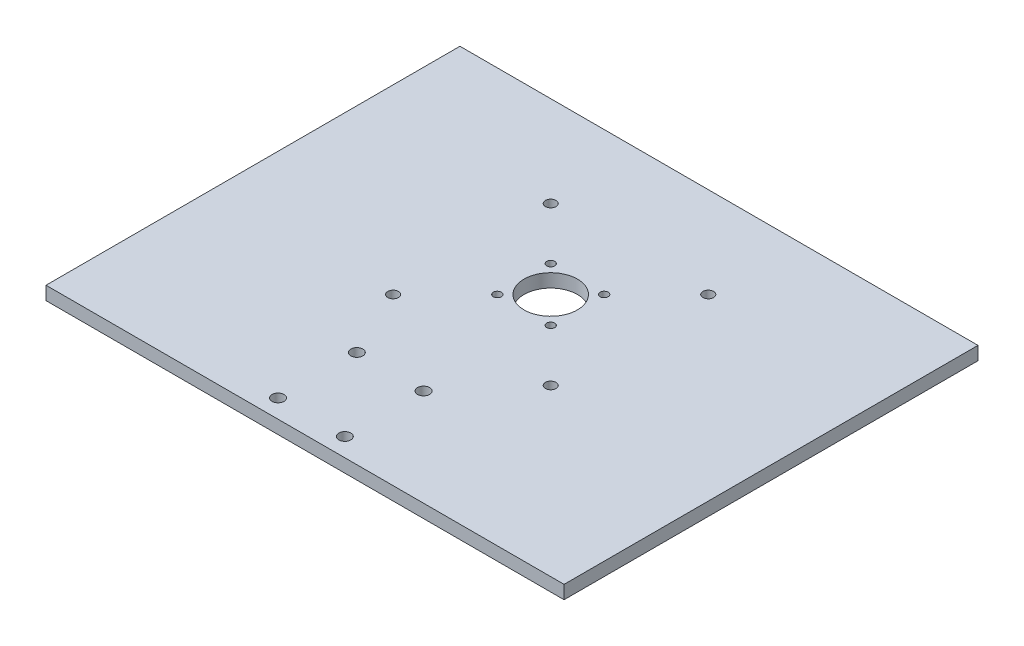
SolidWorks part; units mm, degrees
ref_plane "Front Plane" through (0, 0, 0) normal (0, 0, 1) x (1, 0, 0)
ref_plane "Top Plane" through (0, 0, 0) normal (0, 1, 0) x (1, 0, 0)
ref_plane "Right Plane" through (0, 0, 0) normal (1, 0, 0) x (0, 0, -1)
sketch "Sketch1" plane through (0, 0, 0) normal (0, 1, 0) x (1, 0, 0)
  line L1 (0, 0) -> (194, 0)
  line L2 (0, 0) -> (0, 155)
  line L3 (0, 155) -> (194, 155)
  line L4 (194, 0) -> (194, 155)
  dimension "D1" = 155
  dimension "D2" = 194
extrude "Boss-Extrude1" add sketch "Sketch1" along normal blind 5
sketch "Sketch2" plane through (0, 5, 0) normal (0, 1, 0) x (1, 0, 0)
  line L0 (194, 155) -> (0, 155) construction
  line L1 (0, 0) -> (194, 0) construction
  line L2 (68, 60) -> (68, 64) construction
  line L3 (127, 123) -> (127, 119) construction
  line L4 (70, 62) -> (66, 62) construction
  line L5 (125, 121) -> (129, 121) construction
  line L6 (68, 60) -> (68, 170.8676) construction
  circle A0 centre (68, 121) radius 2
  circle A1 centre (127, 121) radius 2
  circle A2 centre (68, 62) radius 2
  circle A3 centre (127, 62) radius 2
  point P4 (97, 155)
  dimension "D4" = 4
  dimension "D1" = 59
  dimension "D2" = 29
  dimension "D6" = 62
  dimension "D7" = 59
  dimension "D3" = 2
extrude "Cut-Extrude1" cut sketch "Sketch2" against normal through all
sketch "Sketch3" plane through (0, 5, 0) normal (0, 1, 0) x (1, 0, 0)
  circle A0 centre (97.5, 91.5) radius 10
  circle A1 centre (68, 121) radius 2 construction
  circle A3 centre (68, 121) radius 2 construction
  circle A4 centre (107.5, 101.5) radius 1.5
  circle A6 centre (107.5, 81.5) radius 1.5
  circle A8 centre (87.5, 81.5) radius 1.5
  circle A10 centre (87.5, 101.5) radius 1.5
  dimension "D3" = 20
  dimension "D5" = 10
  dimension "D4" = 20
  dimension "D8" = 3
  dimension "D1" = 29.5
  dimension "D2" = 29.5
  dimension "D6" = 10
  dimension "D7" = 10
extrude "Cut-Extrude2" cut sketch "Sketch3" against normal through all
sketch "Sketch4" plane through (0, 0, 0) normal (0, -1, 0) x (-1, 0, 0)
  line L0 (0, 155) -> (0, 0) construction
  circle A0 centre (-80, 6.8964) radius 2.25
  circle A1 centre (-105, 6.8964) radius 2.25
  circle A2 centre (-80, 36.3964) radius 2.25
  circle A3 centre (-105, 36.3964) radius 2.25
  dimension "D1" = 4.5
  dimension "D2" = 80
  dimension "D3" = 29.5
  dimension "D4" = 25
extrude "Cut-Extrude3" cut sketch "Sketch4" against normal through all
